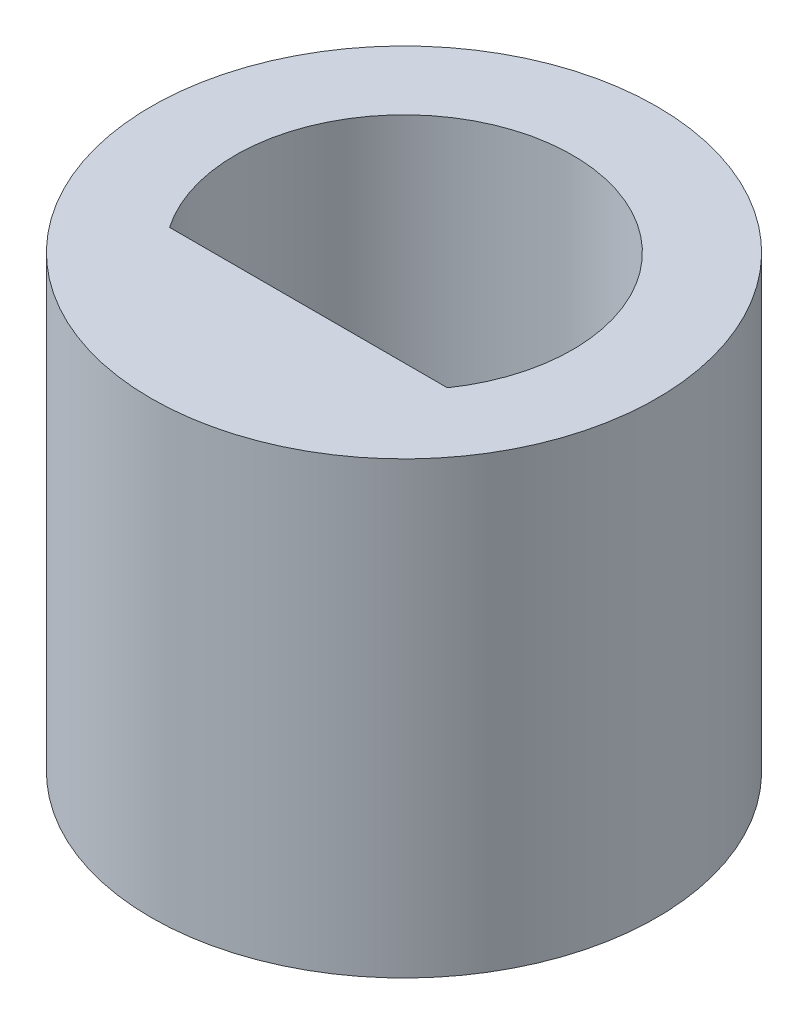
SolidWorks part; units mm, degrees
ref_plane "Front Plane" through (0, 0, 0) normal (0, 0, 1) x (1, 0, 0)
ref_plane "Top Plane" through (0, 0, 0) normal (0, 1, 0) x (1, 0, 0)
ref_plane "Right Plane" through (0, 0, 0) normal (1, 0, 0) x (0, 0, -1)
sketch "Sketch1" plane through (0, 0, 0) normal (0, 1, 0) x (1, 0, 0)
  line L0 (0, 1.5) -> (2.438, 1.5) construction
  line L1 (-1.2359, -0.85) -> (1.2359, -0.85)
  line L2 (0, 2.25) -> (0, 13) construction
  line L3 (-2.5037, 12.7566) -> (-0.635, 2.1585)
  line L4 (2.3787, 12.3726) -> (2.5037, 12.7566)
  line L5 (2.5037, 12.7566) -> (0.635, 2.1585)
  line L6 (11.3586, 6.3232) -> (1.8567, 1.2709)
  line L7 (12.906, 1.5608) -> (2.2491, 0.0631)
  line L8 (9.5237, -8.8487) -> (1.7825, -1.373)
  line L9 (5.4726, -11.792) -> (0.755, -2.1195)
  line L10 (-5.4726, -11.792) -> (-0.755, -2.1195)
  line L11 (-9.5237, -8.8487) -> (-1.7825, -1.373)
  line L12 (-12.906, 1.5608) -> (-2.2491, 0.0631)
  line L13 (-11.3586, 6.3232) -> (-1.8567, 1.2709)
  circle A0 centre (0, 0) radius 1.5
  circle A1 centre (0, 0) radius 2.25
  circle A2 centre (0, 0) radius 13
  circle A3 centre (0, 0) radius 11
  point P35 (0, 0)
  dimension "D1" = 2.35
  dimension "D2" = 10
  dimension "D3" = 10
  dimension "D4" = 0.635
  dimension "D5" = 0.635
  dimension "D6" = 5
extrude "Boss-Extrude1" add sketch "Sketch1" along normal blind 4 contours A1 A0 | L1 A0 region at (0, 0, 1.1155) region at (0, 0, -2.1864)
extrude "Boss-Extrude2" add sketch "Sketch1<4>" along normal blind 0.5 contours A0
sketch "Sketch1<4>" plane through (0, 0, 0) normal (0, 1, 0) x (1, 0, 0) same geometry as "Sketch1"
